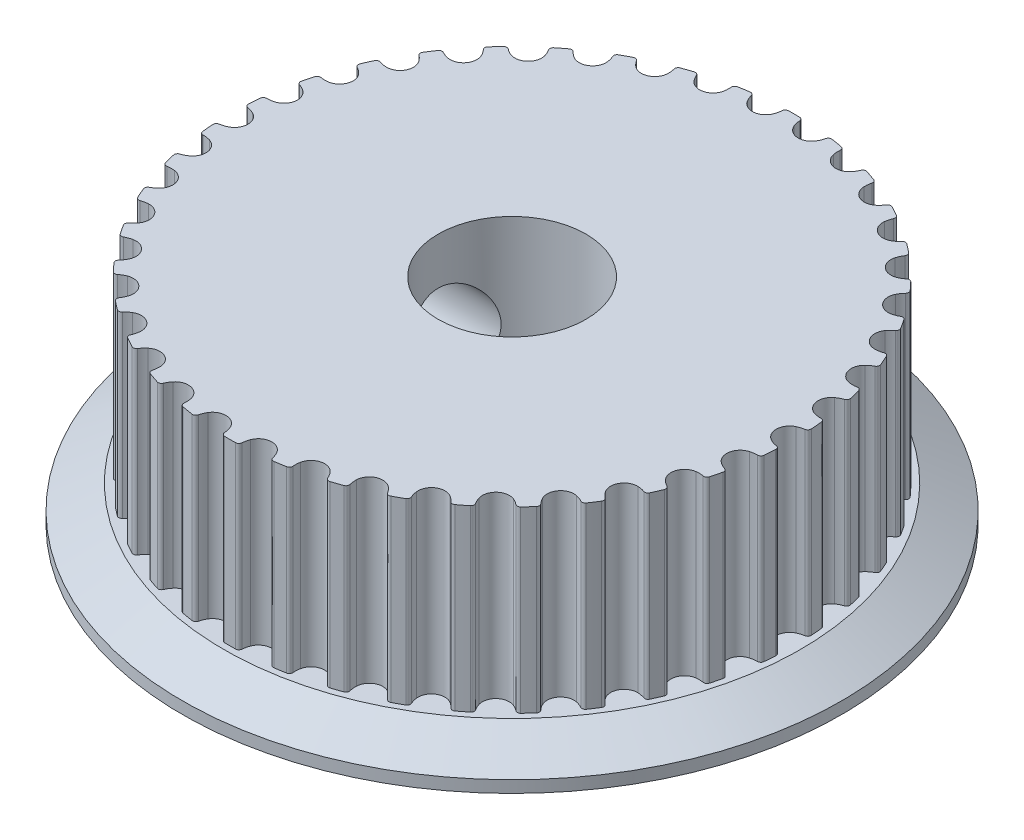
SolidWorks part; units mm, degrees
ref_plane "Front" through (0, 0, 0) normal (0, 0, 1) x (1, 0, 0)
ref_plane "Top" through (0, 0, 0) normal (0, 1, 0) x (1, 0, 0)
ref_plane "Right" through (0, 0, 0) normal (1, 0, 0) x (0, 0, -1)
sketch "Sketch1" plane through (0, 0, 0) normal (0, 1, 0) x (1, 0, 0)
  line L0 (0, 0) -> (0, 12.0958) construction
  line L1 (0, 11.8418) -> (0, 12.4718)
  line L2 (0, 0) -> (0.9989, 12.0545) construction
  line L3 (1.9491, 11.6803) -> (2.0528, 12.3017)
  line L4 (1.3765, 11.7685) -> (1.4052, 12.0139) construction
  arc A0 (0.2321, 11.8395) -> (0.3788, 11.6998) centre (0.2292, 11.6895) cw
  arc A1 (0.3788, 11.6998) -> (0.4446, 11.4056) centre (1.3765, 11.7685) ccw
  circle A2 centre (0, 0) radius 12.0958 construction
  arc A3 (0.2321, 11.8395) -> (0, 11.8418) centre (0, 0) ccw
  arc A4 (0.916, 11.0539) -> (0, 11.0918) centre (0, 0) ccw construction
  arc A5 (0.4446, 11.4056) -> (1.4388, 11.3232) centre (0.9618, 11.607) ccw
  arc A6 (1.3765, 11.7685) -> (0.9785, 11.8082) centre (0, 0) ccw construction
  arc A7 (0, 12.4718) -> (2.0528, 12.3017) centre (0, 0) cw
  arc A8 (1.5521, 11.6026) -> (1.4388, 11.3232) centre (0.5793, 11.8345) cw
  arc A9 (1.7198, 11.7162) -> (1.5521, 11.6026) centre (1.698, 11.5678) ccw
  arc A10 (1.7198, 11.7162) -> (1.9491, 11.6803) centre (0, 0) cw
  dimension "D1" = 0.15
  dimension "D4" = 24.1916
  dimension "D5" = 1
  dimension "D7" = 0.555
  dimension "D3" = 4.737
  dimension "D8" = 0.75
  dimension "D6" = 0.254
  dimension "D2" = 0.4
  dimension "D9" = 1.38
  dimension "D11" = 0.4083
  dimension "D12" = 0.2471
  dimension "D10" = 1.934
sketch "Sketch2" plane through (0, 0, 0) normal (0, 1, 0) x (1, 0, 0)
  circle A0 centre (0, 0) radius 12.0958 construction
  circle A1 centre (0, 0) radius 12.0958
  circle A2 centre (0, 0) radius 3.1
  dimension "D1" = 6.2
extrude "Boss-Extrude1" add sketch "Sketch2" along normal mid plane 10
sketch "Sketch6" plane through (0, 0, 0) normal (0, 1, 0) x (1, 0, 0)
  line L0 (0, 11.8318) -> (0, 12.4718)
  line L1 (1.9474, 11.6704) -> (2.0528, 12.3017)
  arc A7 (2.0528, 12.3017) -> (0, 12.4718) centre (0, 0) ccw construction
  arc A8 (2.0528, 12.3017) -> (0, 12.4718) centre (0, 0) ccw
  arc A14 (1.7183, 11.7063) -> (1.5618, 11.6003) centre (1.698, 11.5678) ccw
  arc A15 (1.4474, 11.3181) -> (1.5618, 11.6003) centre (0.5793, 11.8345) ccw
  arc A16 (0.4353, 11.402) -> (1.4474, 11.3181) centre (0.9618, 11.607) ccw
  arc A17 (0.3688, 11.6991) -> (0.4353, 11.402) centre (1.3765, 11.7685) ccw
  arc A18 (0.3688, 11.6991) -> (0.2319, 11.8295) centre (0.2292, 11.6895) ccw
  arc A19 (0.2319, 11.8295) -> (0, 11.8318) centre (0, 0) ccw
  arc A20 (1.9474, 11.6704) -> (1.7183, 11.7063) centre (0, 0) ccw
  arc A21 (1.7183, 11.7063) -> (1.5618, 11.6003) centre (1.698, 11.5678) ccw
  arc A22 (1.4474, 11.3181) -> (1.5618, 11.6003) centre (0.5793, 11.8345) ccw
  arc A23 (0.4353, 11.402) -> (1.4474, 11.3181) centre (0.9618, 11.607) ccw
  arc A24 (0.3688, 11.6991) -> (0.4353, 11.402) centre (1.3765, 11.7685) ccw
  arc A25 (0.3688, 11.6991) -> (0.2319, 11.8295) centre (0.2292, 11.6895) ccw
  arc A26 (0.2319, 11.8295) -> (0, 11.8318) centre (0, 0) ccw
  arc A27 (1.9474, 11.6704) -> (1.7183, 11.7063) centre (0, 0) ccw
extrude "Cut-Extrude3" cut sketch "Sketch6" against normal through all both and the other way through all
pattern_circular "CirPattern3" count 38 over 360 about axis through (0, 5, 0) along (0, -1, 0) of "Cut-Extrude3"
sketch "Sketch3" plane through (0, 0, 0) normal (0, 0, 1) x (1, 0, 0)
  line L0 (0, 0) -> (0, 9.5108) construction
  line L1 (-12.0958, 5) -> (-13.8278, 6)
  line L2 (-13.8278, 6) -> (-13.8278, 6.5)
  line L3 (-13.8278, 6.5) -> (-3.1, 6.5)
  line L4 (-3.1, 6.5) -> (-3.1, 5)
  line L5 (-3.1, 5) -> (-12.0958, 5)
  line L6 (3.1, 5) -> (-3.1, 5) construction
  dimension "D4" = 24.1916
  dimension "D1" = 1.5
  dimension "D2" = 0.5
  dimension "D3" = 30
revolve "Revolve1" add sketch "Sketch3" angle 360 about L0
mirror "Mirror1" about plane through (0, 0, 0) normal (0, 1, 0) of "Revolve1"
sketch "Sketch4" plane through (0, 0, 0) normal (0, 0, 1) x (1, 0, 0)
  line L0 (0, 0) -> (0, 14.0175) construction
  line L1 (13.8278, 6.5) -> (-13.8278, 6.5) construction
  line L2 (-3.1, 6.5) -> (-9.6, 6.5)
  line L3 (-3.1, 6.5) -> (-3.1, 12.5)
  line L4 (-3.1, 12.5) -> (-9.6, 12.5)
  line L5 (-9.6, 6.5) -> (-9.6, 12.5)
  dimension "D2" = 6
  dimension "D1" = 6.5
revolve "Revolve2" add sketch "Sketch4" angle 360 about L0
sketch "Sketch5" plane through (0, 0, 0) normal (0, 0, 1) x (1, 0, 0)
  line L1 (0, 6.5) -> (0, 12.5) construction
  line L2 (9.6, 12.5) -> (-9.6, 12.5) construction
  line L7 (-9.6, 12.5) -> (-9.6, 6.5) construction
  line L8 (-9.6, 12.5) -> (-9.6, 6.5) construction
  circle A0 centre (0, 9.5) radius 1.6
  dimension "D1" = 3.2
extrude "Cut-Extrude2" cut sketch "Sketch5" along normal through all
pattern_circular "CirPattern2" count 2 over 90 about axis through (0, 5, 0) along (0, -1, 0) of "Cut-Extrude2" reverse direction yes
sketch "Sketch7" plane through (0, 12.5, 0) normal (0, 1, 0) x (1, 0, 0)
  circle A0 centre (0, 0) radius 18
extrude "Cut-Extrude4" cut sketch "Sketch7" against normal blind 10
sketch "Sketch8" plane through (0, 0, 0) normal (1, 0, 0) x (0, 0, -1)
  circle A0 centre (0, -1.4146) radius 1.95
  dimension "D1" = 3.9
extrude "Cut-Extrude5" cut sketch "Sketch8" against normal through all
sketch "Sketch10" plane through (0, 0, 0) normal (1, 0, 0) x (0, 0, -1)
  circle A0 centre (0, -1.4146) radius 2.75
  dimension "D1" = 5.5
extrude "Cut-Extrude6" cut sketch "Sketch10" against normal blind 10 from offset 8 offset against normal yes
equation "\"belt-step\"= 2"
equation "\"pulley-teeth\"= 38"
equation "\"pulley-dia\"= ( \"belt-step\" * \"pulley-teeth\" ) / Pi"
equation "\"D3@Sketch1\"=(360/\"pulley-teeth\")/2"
equation "\"D4@Sketch1\"=\"pulley-dia\""
equation "\"bore-dia\"= 6.2"
equation "\"belt-thick\"= 10"
equation "\"D4@Sketch3\"=\"pulley-dia\""
equation "\"D1@Sketch2\"=\"bore-dia\""
equation "\"D1@Boss-Extrude1\"=\"belt-thick\""
equation "\"teeth-offset\"= 0.01"
equation "\"D1@Sketch6\"=\"teeth-offset\""
equation "\"D1@CirPattern3\"=\"pulley-teeth\""
equation "\"flange-wall\"= 6.5"
equation "\"D1@Sketch4\"=\"flange-wall\""
equation "\"flange-h\"= 6"
equation "\"screw-dia\"= 3.2"
equation "\"D2@Sketch4\"=\"flange-h\""
equation "\"D1@Sketch5\"=\"screw-dia\""
equation "\"D10@Sketch1\"=(0.4/(Pi*(\"pulley-dia\"-(2*\"D12@Sketch1\"))))*360"
